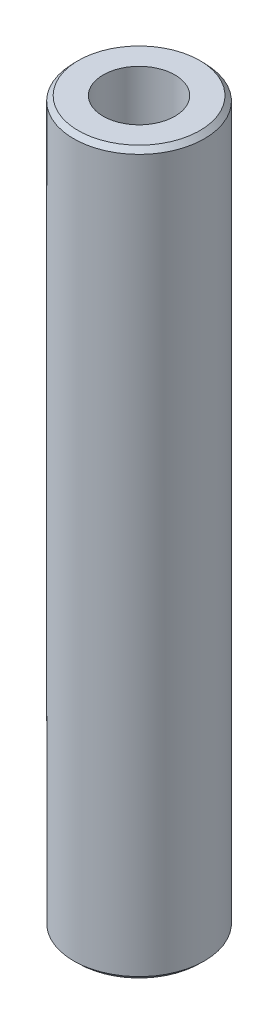
SolidWorks part; units mm, degrees
ref_plane "Front Plane" through (0, 0, 0) normal (0, 0, 1) x (1, 0, 0)
ref_plane "Top Plane" through (0, 0, 0) normal (0, 1, 0) x (1, 0, 0)
ref_plane "Right Plane" through (0, 0, 0) normal (1, 0, 0) x (0, 0, -1)
sketch "Sketch1" plane through (0, 0, 0) normal (0, 1, 0) x (1, 0, 0)
  circle A0 centre (0, 0) radius 40
  dimension "SHAFT_OD" = 80
extrude "Boss-Extrude1" add sketch "Sketch1" along normal blind 441.5419
sketch "Sketch2" plane through (0, 0, 0) normal (0, 1, 0) x (1, 0, 0)
  circle A0 centre (0, 0) radius 21.9501
  dimension "BORE_D" = 43.9002
extrude "Cut-Extrude1" cut sketch "Sketch2" along normal through all
chamfer "Chamfer1" distance 2.9053 angle 44.01 2 edges at (0, 441.5419, 40) (0, 0, 40) first distance on face at (0, 441.5419, 40) first distance on face at (0, 0, 21.9501)
